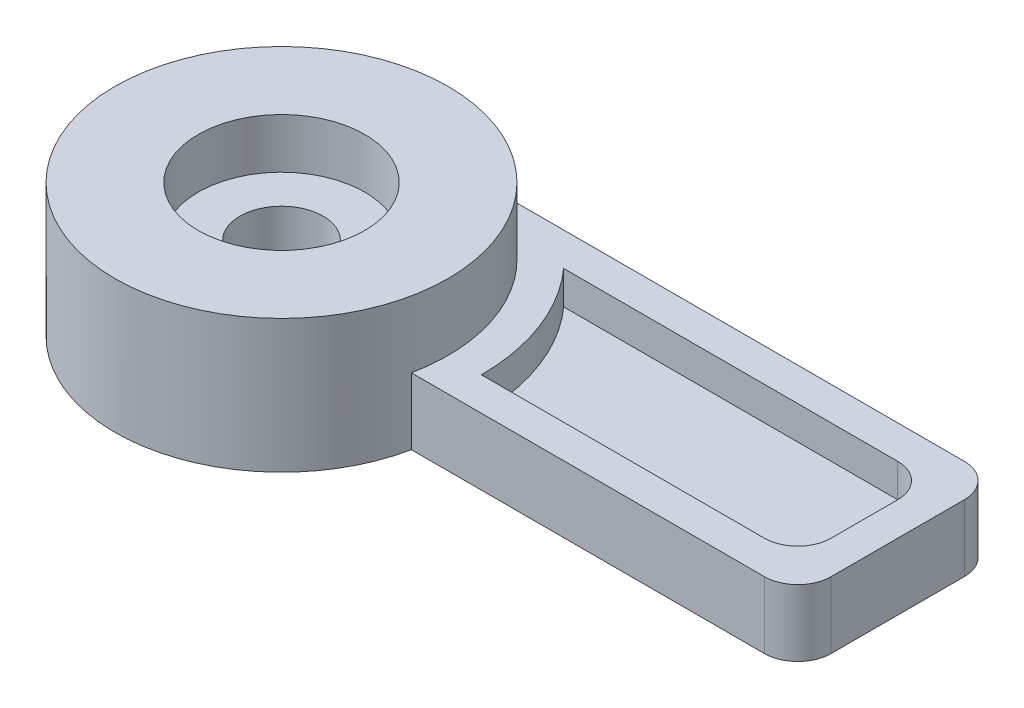
SolidWorks part; units mm, degrees
ref_plane "정면" through (0, 0, 0) normal (0, 0, 1) x (1, 0, 0)
ref_plane "윗면" through (0, 0, 0) normal (0, 1, 0) x (1, 0, 0)
ref_plane "우측면" through (0, 0, 0) normal (1, 0, 0) x (0, 0, -1)
sketch "스케치2" plane through (0, 0, 0) normal (0, 1, 0) x (1, 0, 0)
  line L0 (0, 50) -> (165, 50)
  line L1 (165, 50) -> (165, -10)
  line L2 (165, -10) -> (48.9898, -10)
  line L3 (44.7214, 40) -> (155, 40)
  line L4 (155, 40) -> (155, 0)
  line L5 (155, 0) -> (60, 0)
  line L6 (0, 40) -> (155, 40) construction
  line L8 (155, 0) -> (48.9898, 0) construction
  circle A0 centre (0, 0) radius 50
  arc A1 (60, 0) -> (44.7214, 40) centre (0, 0) ccw
  circle A2 centre (0, 0) radius 60 construction
  dimension "D1" = 100
  dimension "D2" = 165
  dimension "D3" = 60
  dimension "D4" = 10
extrude "보스-돌출1" add sketch "스케치2" along normal blind 20 contours A0 L2 L1 L0 L5 A1 L3 L4 region at (82.5, 0, -48.2443)
extrude "보스-돌출2" add sketch "스케치2<4>" along normal blind 40 contours A0 region at (0, 0, 0)
sketch "스케치2<4>" plane through (0, 0, 0) normal (0, 1, 0) x (1, 0, 0) same geometry as "스케치2"
extrude "보스-돌출3" add sketch "스케치2<5>" along normal blind 10 contours L3 L4 L5 A1
sketch "스케치2<5>" plane through (0, 0, 0) normal (0, 1, 0) x (1, 0, 0) same geometry as "스케치2"
fillet "필렛1" radius 10 4 edges at (165, 10, -50) (155, 15, -40) (155, 15, 0) (165, 10, 10)
hole_wizard "M1.6 남비 머리 나사용 카운터보어1" positions "스케치4" profile "스케치3" counterbore size "M1.6" standard "ISO" end condition through all
sketch "스케치4" plane through (0, 40, 0) normal (0, 1, 0) x (1, 0, 0)
  point P0 (0, 0)
sketch "스케치3" plane through (0, 40, 0) normal (1, 0, 0) x (0, 0, 1)
  line L0 (0, 0) -> (0, 40)
  line L1 (0, 40) -> (12.5, 40)
  line L3 (12.5, 40) -> (12.5, 15)
  line L4 (12.5, 15) -> (25, 15)
  line L5 (25, 15) -> (25, 0)
  line L7 (25, 0) -> (0, 0)
  line L11 (0, -6.35) -> (0, 107.95) construction
  dimension "관통 구멍 지름" = 25
  dimension "관통 구멍 깊이" = 40
  dimension "카운터보어 지름" = 50
  dimension "카운터보어 깊이" = 15
